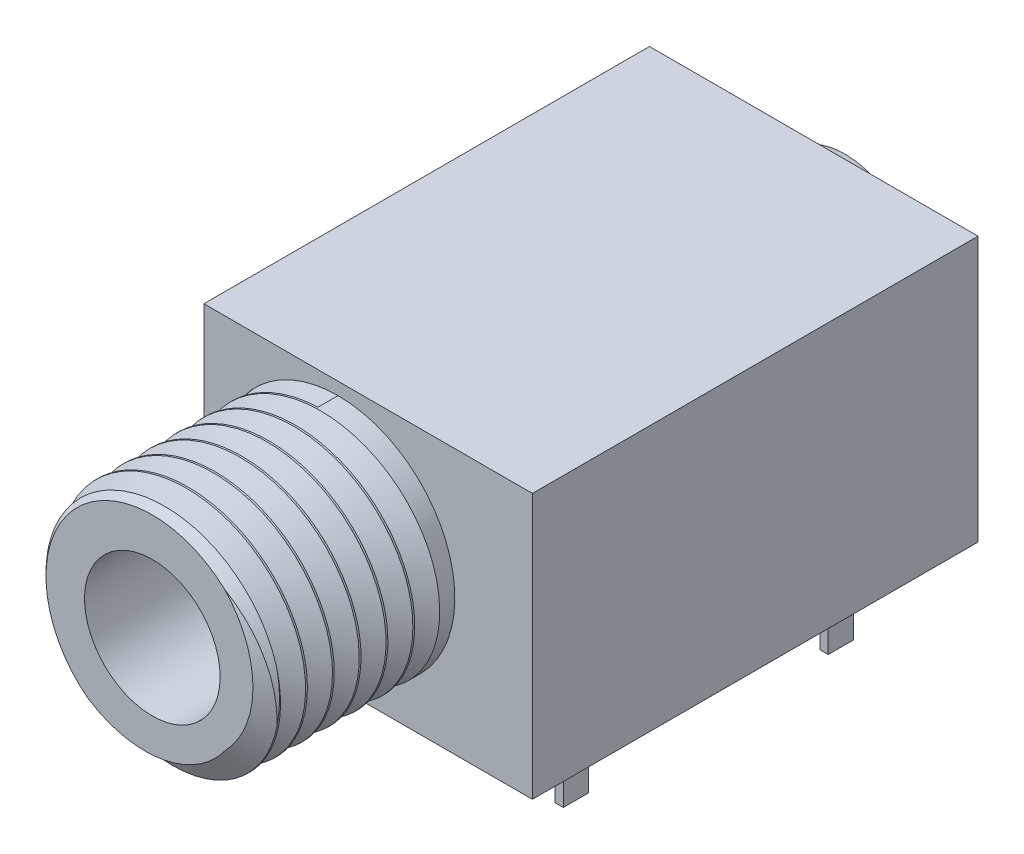
SolidWorks part; units mm, degrees
ref_plane "Front Plane" through (0, 0, 0) normal (0, 0, 1) x (1, 0, 0)
ref_plane "Top Plane" through (0, 0, 0) normal (0, 1, 0) x (1, 0, 0)
ref_plane "Right Plane" through (0, 0, 0) normal (1, 0, 0) x (0, 0, -1)
sketch "Sketch1" plane through (0, 0, 0) normal (0, 1, 0) x (1, 0, 0)
  line L1 (-14.6008, 12.6317) -> (1.1492, 12.6317)
  line L2 (-14.6008, 12.6317) -> (-14.6008, -8.7283)
  line L3 (-14.6008, -8.7283) -> (1.1492, -8.7283)
  line L4 (1.1492, 12.6317) -> (1.1492, -8.7283)
  dimension "D1" = 15.75
  dimension "D2" = 21.36
extrude "Boss-Extrude1" add sketch "Sketch1" along normal blind 12.7
sketch "Sketch3" plane through (0, 0, -12.6317) normal (0, 0, -1) x (-1, 0, 0)
  line L0 (-1.1492, 0) -> (14.6008, 0) construction
  line L1 (14.6008, 12.7) -> (14.6008, 0) construction
  circle A0 centre (8.1708, 6.5) radius 4
  dimension "D1" = 6.5
  dimension "D2" = 6.43
extrude "Boss-Extrude2" add sketch "Sketch3" along normal blind 2.94 draft 10
sketch "Sketch4" plane through (0, 0, 8.7283) normal (0, 0, 1) x (1, 0, 0)
  line L0 (-14.6008, 12.7) -> (-14.6008, 0) construction
  line L1 (-14.6008, 0) -> (1.1492, 0) construction
  circle A0 centre (-8.1708, 6.5) radius 5.6
  dimension "D1" = 6.43
  dimension "D2" = 6.5
extrude "Boss-Extrude3" add sketch "Sketch4" along normal blind 8.9
chamfer "Chamfer1" distance 0.5 angle 45 1 edges at (-2.5708, 6.5, 17.6283)
ref_plane "Plane1" through (0, 6.5, 0) normal (0, -1, 0) x (-1, 0, 0)
sketch "Sketch6" plane through (0, 6.5, 0) normal (0, -1, 0) x (-1, 0, 0)
  line L0 (13.7708, -16.5283) -> (13.7708, -17.7283)
  line L1 (13.7708, -17.1283) -> (13.7708, -8.7283) construction
  line L2 (2.5708, -17.1283) -> (13.7708, -17.1283) construction
  line L3 (13.7708, -17.7283) -> (12.7315, -17.1283)
  line L4 (12.7315, -17.1283) -> (13.7708, -16.5283)
  line L5 (8.1708, -18.6021) -> (8.1708, -10.6988) construction
  point P4 (13.7708, -17.1283)
  dimension "D1" = 5.6
  dimension "D3" = 1.2
sketch "Sketch9" plane through (0, 0, 17.6283) normal (0, 0, 1) x (1, 0, 0)
  circle A0 centre (-8.1708, 6.5) radius 5.6
curve "Helix/Spiral1" pitch 1.2857 height 9 turns 7
sweep "Cut-Sweep1" cut profiles "Sketch6" path "Helix/Spiral1" align with end faces yes
sketch "Sketch13" plane through (0, 0, 17.6283) normal (0, 0, 1) x (1, 0, 0)
  circle A0 centre (-8.1708, 6.5) radius 3.25
  dimension "D1" = 6.5
extrude "Cut-Extrude1" cut sketch "Sketch13" against normal blind 29
sketch "Sketch14" plane through (0, 0, 0) normal (0, -1, 0) x (1, 0, 0)
  line L0 (-6.9358, -12.6317) -> (-6.9358, 8.7283) construction
  line L1 (-12.8508, 5.0783) -> (-12.4508, 5.0783)
  line L2 (-12.8508, 5.0783) -> (-12.8508, 3.8783)
  line L3 (-12.8508, 3.8783) -> (-12.4508, 3.8783)
  line L4 (-12.4508, 5.0783) -> (-12.4508, 3.8783)
  line L5 (-12.4508, -7.6217) -> (-12.4508, -8.8217)
  line L6 (-8.2508, -1.3881) -> (-8.2508, 3.8102) construction
  line L7 (-12.8508, -7.6217) -> (-12.8508, -8.8217)
  line L8 (-12.8508, -8.8217) -> (-12.4508, -8.8217)
  line L9 (-12.8508, -7.6217) -> (-12.4508, -7.6217)
  line L10 (-1.0208, -8.8217) -> (-1.4208, -8.8217)
  line L11 (-1.0208, 3.8783) -> (-1.4208, 3.8783)
  line L12 (-1.0208, 5.0783) -> (-1.0208, 3.8783)
  line L13 (-1.4208, 5.0783) -> (-1.4208, 3.8783)
  line L14 (-1.0208, 5.0783) -> (-1.4208, 5.0783)
  line L15 (-1.0208, -7.6217) -> (-1.0208, -8.8217)
  line L16 (-1.0208, -7.6217) -> (-1.4208, -7.6217)
  line L17 (-14.6008, -12.6317) -> (-14.6008, 8.7283) construction
  line L18 (-14.6008, 8.7283) -> (1.1492, 8.7283) construction
  line L19 (-1.4208, -7.6217) -> (-1.4208, -8.8217)
  dimension "D1" = 1.2
  dimension "D2" = 0.4
  dimension "D3" = 2
  dimension "D4" = 5.515
  dimension "D5" = 6.35
  dimension "D6" = 4.2
  dimension "D7" = 3.65
extrude "Boss-Extrude4" add sketch "Sketch14" along normal blind 3.25
